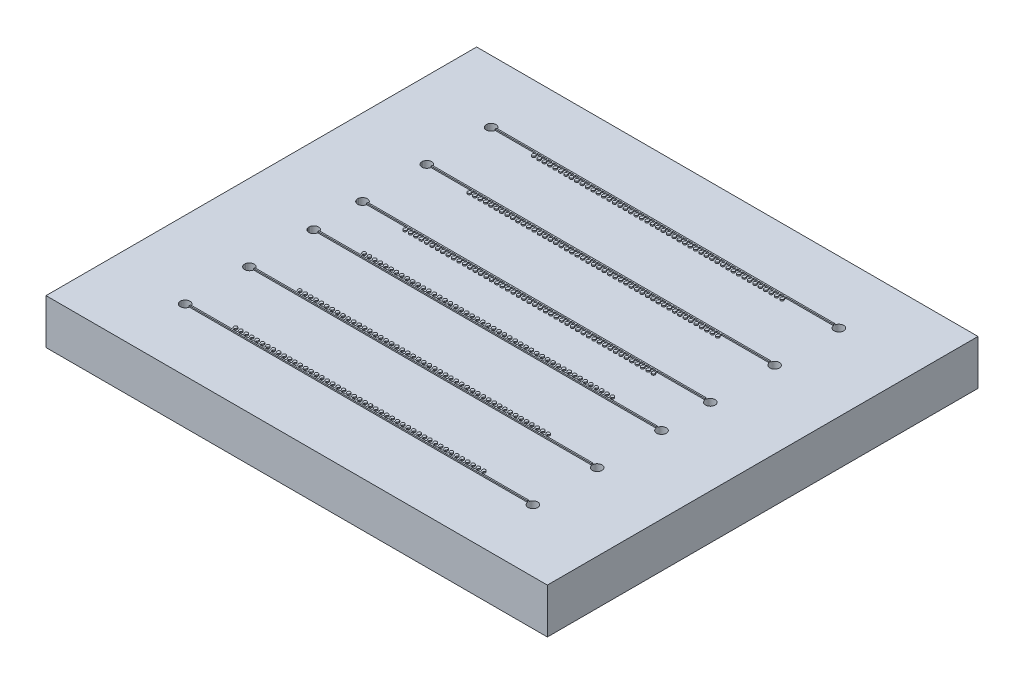
SolidWorks part; units mm, degrees
ref_plane "Front Plane" through (0, 0, 0) normal (0, 0, 1) x (1, 0, 0)
ref_plane "Top Plane" through (0, 0, 0) normal (0, 1, 0) x (1, 0, 0)
ref_plane "Right Plane" through (0, 0, 0) normal (1, 0, 0) x (0, 0, -1)
sketch "Sketch1" plane through (0, 0, 0) normal (0, 1, 0) x (1, 0, 0)
  line L1 (-19.5, 16.75) -> (19.5, 16.75)
  line L2 (-19.5, 16.75) -> (-19.5, -16.75)
  line L3 (-19.5, -16.75) -> (19.5, -16.75)
  line L4 (19.5, 16.75) -> (19.5, -16.75)
  line L5 (-19.5, 16.75) -> (19.5, -16.75) construction
  line L6 (-19.5, -16.75) -> (19.5, 16.75) construction
  point P0 (0, 0)
  dimension "D1" = 33.5
  dimension "D2" = 39
extrude "Boss-Extrude1" add sketch "Sketch1" along normal blind 3.5
sketch "Sketch2" plane through (0, 3.5, 0) normal (0, 1, 0) x (1, 0, 0)
  line L0 (0, -1000) -> (0, 49000) construction
  line L1 (-13.1533, 12.4873) -> (-13.1533, 11.3127) construction
  line L2 (-9.02, 11.85) -> (-9.02, 11.71)
  line L3 (-19.5, 0) -> (19.5, 0) construction
  line L4 (-19.5, 16.75) -> (-19.5, -16.75) construction
  line L5 (19.5, -16.75) -> (19.5, 16.75) construction
  line L6 (-9.12, 11.85) -> (-9.12, 11.71)
  line L7 (-9.44, 11.85) -> (-9.12, 11.85)
  line L8 (-13.9, 11.95) -> (13.9, 11.95)
  line L9 (19.5, 16.75) -> (-19.5, 16.75) construction
  line L10 (-13.9, 11.95) -> (-13.9, 11.85)
  line L11 (-13.9, 11.85) -> (-9.96, 11.85)
  line L12 (-9.96, 11.85) -> (-9.96, 11.71)
  line L13 (-9.86, 11.71) -> (-9.86, 11.85)
  line L14 (-9.86, 11.85) -> (-9.54, 11.85)
  line L15 (-9.54, 11.85) -> (-9.54, 11.71)
  line L16 (-9.44, 11.85) -> (-9.44, 11.71)
  line L17 (-8.6, 11.85) -> (-8.6, 11.71)
  line L18 (-8.7, 11.85) -> (-8.7, 11.71)
  line L19 (-9.02, 11.85) -> (-8.7, 11.85)
  line L20 (-8.18, 11.85) -> (-8.18, 11.71)
  line L21 (-8.28, 11.85) -> (-8.28, 11.71)
  line L22 (-8.6, 11.85) -> (-8.28, 11.85)
  line L23 (-7.76, 11.85) -> (-7.76, 11.71)
  line L24 (-7.86, 11.85) -> (-7.86, 11.71)
  line L25 (-8.18, 11.85) -> (-7.86, 11.85)
  line L26 (-7.34, 11.85) -> (-7.34, 11.71)
  line L27 (-7.44, 11.85) -> (-7.44, 11.71)
  line L28 (-7.76, 11.85) -> (-7.44, 11.85)
  line L29 (-6.92, 11.85) -> (-6.92, 11.71)
  line L30 (-7.02, 11.85) -> (-7.02, 11.71)
  line L31 (-7.34, 11.85) -> (-7.02, 11.85)
  line L32 (-6.5, 11.85) -> (-6.5, 11.71)
  line L33 (-6.6, 11.85) -> (-6.6, 11.71)
  line L34 (-6.92, 11.85) -> (-6.6, 11.85)
  line L35 (-6.08, 11.85) -> (-6.08, 11.71)
  line L36 (-6.18, 11.85) -> (-6.18, 11.71)
  line L37 (-6.5, 11.85) -> (-6.18, 11.85)
  line L38 (-5.66, 11.85) -> (-5.66, 11.71)
  line L39 (-5.76, 11.85) -> (-5.76, 11.71)
  line L40 (-6.08, 11.85) -> (-5.76, 11.85)
  line L41 (-5.24, 11.85) -> (-5.24, 11.71)
  line L42 (-5.34, 11.85) -> (-5.34, 11.71)
  line L43 (-5.66, 11.85) -> (-5.34, 11.85)
  line L44 (-4.82, 11.85) -> (-4.82, 11.71)
  line L45 (-4.92, 11.85) -> (-4.92, 11.71)
  line L46 (-5.24, 11.85) -> (-4.92, 11.85)
  line L47 (-4.4, 11.85) -> (-4.4, 11.71)
  line L48 (-4.5, 11.85) -> (-4.5, 11.71)
  line L49 (-4.82, 11.85) -> (-4.5, 11.85)
  line L50 (-3.98, 11.85) -> (-3.98, 11.71)
  line L51 (-4.08, 11.85) -> (-4.08, 11.71)
  line L52 (-4.4, 11.85) -> (-4.08, 11.85)
  line L53 (-3.56, 11.85) -> (-3.56, 11.71)
  line L54 (-3.66, 11.85) -> (-3.66, 11.71)
  line L55 (-3.98, 11.85) -> (-3.66, 11.85)
  line L56 (-3.14, 11.85) -> (-3.14, 11.71)
  line L57 (-3.24, 11.85) -> (-3.24, 11.71)
  line L58 (-3.56, 11.85) -> (-3.24, 11.85)
  line L59 (-2.72, 11.85) -> (-2.72, 11.71)
  line L60 (-2.82, 11.85) -> (-2.82, 11.71)
  line L61 (-3.14, 11.85) -> (-2.82, 11.85)
  line L62 (-2.3, 11.85) -> (-2.3, 11.71)
  line L63 (-2.4, 11.85) -> (-2.4, 11.71)
  line L64 (-2.72, 11.85) -> (-2.4, 11.85)
  line L65 (-1.88, 11.85) -> (-1.88, 11.71)
  line L66 (-1.98, 11.85) -> (-1.98, 11.71)
  line L67 (-2.3, 11.85) -> (-1.98, 11.85)
  line L68 (-1.46, 11.85) -> (-1.46, 11.71)
  line L69 (-1.56, 11.85) -> (-1.56, 11.71)
  line L70 (-1.88, 11.85) -> (-1.56, 11.85)
  line L71 (-1.04, 11.85) -> (-1.04, 11.71)
  line L72 (-1.14, 11.85) -> (-1.14, 11.71)
  line L73 (-1.46, 11.85) -> (-1.14, 11.85)
  line L74 (-0.62, 11.85) -> (-0.62, 11.71)
  line L75 (-0.72, 11.85) -> (-0.72, 11.71)
  line L76 (-1.04, 11.85) -> (-0.72, 11.85)
  line L77 (-0.2, 11.85) -> (-0.2, 11.71)
  line L78 (-0.3, 11.85) -> (-0.3, 11.71)
  line L79 (-0.62, 11.85) -> (-0.3, 11.85)
  line L80 (0.22, 11.85) -> (0.22, 11.71)
  line L81 (0.12, 11.85) -> (0.12, 11.71)
  line L82 (-0.2, 11.85) -> (0.12, 11.85)
  line L83 (0.64, 11.85) -> (0.64, 11.71)
  line L84 (0.54, 11.85) -> (0.54, 11.71)
  line L85 (0.22, 11.85) -> (0.54, 11.85)
  line L86 (1.06, 11.85) -> (1.06, 11.71)
  line L87 (0.96, 11.85) -> (0.96, 11.71)
  line L88 (0.64, 11.85) -> (0.96, 11.85)
  line L89 (1.48, 11.85) -> (1.48, 11.71)
  line L90 (1.38, 11.85) -> (1.38, 11.71)
  line L91 (1.06, 11.85) -> (1.38, 11.85)
  line L92 (1.9, 11.85) -> (1.9, 11.71)
  line L93 (1.8, 11.85) -> (1.8, 11.71)
  line L94 (1.48, 11.85) -> (1.8, 11.85)
  line L95 (2.32, 11.85) -> (2.32, 11.71)
  line L96 (2.22, 11.85) -> (2.22, 11.71)
  line L97 (1.9, 11.85) -> (2.22, 11.85)
  line L98 (2.74, 11.85) -> (2.74, 11.71)
  line L99 (2.64, 11.85) -> (2.64, 11.71)
  line L100 (2.32, 11.85) -> (2.64, 11.85)
  line L101 (3.16, 11.85) -> (3.16, 11.71)
  line L102 (3.06, 11.85) -> (3.06, 11.71)
  line L103 (2.74, 11.85) -> (3.06, 11.85)
  line L104 (3.58, 11.85) -> (3.58, 11.71)
  line L105 (3.48, 11.85) -> (3.48, 11.71)
  line L106 (3.16, 11.85) -> (3.48, 11.85)
  line L107 (4, 11.85) -> (4, 11.71)
  line L108 (3.9, 11.85) -> (3.9, 11.71)
  line L109 (3.58, 11.85) -> (3.9, 11.85)
  line L110 (4.42, 11.85) -> (4.42, 11.71)
  line L111 (4.32, 11.85) -> (4.32, 11.71)
  line L112 (4, 11.85) -> (4.32, 11.85)
  line L113 (4.84, 11.85) -> (4.84, 11.71)
  line L114 (4.74, 11.85) -> (4.74, 11.71)
  line L115 (4.42, 11.85) -> (4.74, 11.85)
  line L116 (5.26, 11.85) -> (5.26, 11.71)
  line L117 (5.16, 11.85) -> (5.16, 11.71)
  line L118 (4.84, 11.85) -> (5.16, 11.85)
  line L119 (5.68, 11.85) -> (5.68, 11.71)
  line L120 (5.58, 11.85) -> (5.58, 11.71)
  line L121 (5.26, 11.85) -> (5.58, 11.85)
  line L122 (6.1, 11.85) -> (6.1, 11.71)
  line L123 (6, 11.85) -> (6, 11.71)
  line L124 (5.68, 11.85) -> (6, 11.85)
  line L125 (6.52, 11.85) -> (6.52, 11.71)
  line L126 (6.42, 11.85) -> (6.42, 11.71)
  line L127 (6.1, 11.85) -> (6.42, 11.85)
  line L128 (6.94, 11.85) -> (6.94, 11.71)
  line L129 (6.84, 11.85) -> (6.84, 11.71)
  line L130 (6.52, 11.85) -> (6.84, 11.85)
  line L131 (7.36, 11.85) -> (7.36, 11.71)
  line L132 (7.26, 11.85) -> (7.26, 11.71)
  line L133 (6.94, 11.85) -> (7.26, 11.85)
  line L134 (7.78, 11.85) -> (7.78, 11.71)
  line L135 (7.68, 11.85) -> (7.68, 11.71)
  line L136 (7.36, 11.85) -> (7.68, 11.85)
  line L137 (8.2, 11.85) -> (8.2, 11.71)
  line L138 (8.1, 11.85) -> (8.1, 11.71)
  line L139 (7.78, 11.85) -> (8.1, 11.85)
  line L140 (8.62, 11.85) -> (8.62, 11.71)
  line L141 (8.52, 11.85) -> (8.52, 11.71)
  line L142 (8.2, 11.85) -> (8.52, 11.85)
  line L143 (9.04, 11.85) -> (9.04, 11.71)
  line L144 (8.94, 11.85) -> (8.94, 11.71)
  line L145 (8.62, 11.85) -> (8.94, 11.85)
  line L146 (9.46, 11.85) -> (9.46, 11.71)
  line L147 (9.36, 11.85) -> (9.36, 11.71)
  line L148 (9.04, 11.85) -> (9.36, 11.85)
  line L149 (-9.44, 11.85) -> (-9.02, 11.85) construction
  line L150 (9.46, 11.85) -> (13.9, 11.85)
  line L151 (13.9, 11.85) -> (13.9, 11.95)
  line L152 (13.1533, 12.6013) -> (13.1533, 11.1987) construction
  arc A0 (-9.96, 11.71) -> (-9.86, 11.71) centre (-9.91, 11.5965) ccw
  arc A1 (-9.54, 11.71) -> (-9.44, 11.71) centre (-9.49, 11.5965) ccw
  circle A2 centre (-13.5283, 11.9) radius 0.375
  arc A3 (-9.12, 11.71) -> (-9.02, 11.71) centre (-9.07, 11.5965) ccw
  arc A4 (-8.7, 11.71) -> (-8.6, 11.71) centre (-8.65, 11.5965) ccw
  arc A5 (-8.28, 11.71) -> (-8.18, 11.71) centre (-8.23, 11.5965) ccw
  arc A6 (-7.86, 11.71) -> (-7.76, 11.71) centre (-7.81, 11.5965) ccw
  arc A7 (-7.44, 11.71) -> (-7.34, 11.71) centre (-7.39, 11.5965) ccw
  arc A8 (-7.02, 11.71) -> (-6.92, 11.71) centre (-6.97, 11.5965) ccw
  arc A9 (-6.6, 11.71) -> (-6.5, 11.71) centre (-6.55, 11.5965) ccw
  arc A10 (-6.18, 11.71) -> (-6.08, 11.71) centre (-6.13, 11.5965) ccw
  arc A11 (-5.76, 11.71) -> (-5.66, 11.71) centre (-5.71, 11.5965) ccw
  arc A12 (-5.34, 11.71) -> (-5.24, 11.71) centre (-5.29, 11.5965) ccw
  arc A13 (-4.92, 11.71) -> (-4.82, 11.71) centre (-4.87, 11.5965) ccw
  arc A14 (-4.5, 11.71) -> (-4.4, 11.71) centre (-4.45, 11.5965) ccw
  arc A15 (-4.08, 11.71) -> (-3.98, 11.71) centre (-4.03, 11.5965) ccw
  arc A16 (-3.66, 11.71) -> (-3.56, 11.71) centre (-3.61, 11.5965) ccw
  arc A17 (-3.24, 11.71) -> (-3.14, 11.71) centre (-3.19, 11.5965) ccw
  arc A18 (-2.82, 11.71) -> (-2.72, 11.71) centre (-2.77, 11.5965) ccw
  arc A19 (-2.4, 11.71) -> (-2.3, 11.71) centre (-2.35, 11.5965) ccw
  arc A20 (-1.98, 11.71) -> (-1.88, 11.71) centre (-1.93, 11.5965) ccw
  arc A21 (-1.56, 11.71) -> (-1.46, 11.71) centre (-1.51, 11.5965) ccw
  arc A22 (-1.14, 11.71) -> (-1.04, 11.71) centre (-1.09, 11.5965) ccw
  arc A23 (-0.72, 11.71) -> (-0.62, 11.71) centre (-0.67, 11.5965) ccw
  arc A24 (-0.3, 11.71) -> (-0.2, 11.71) centre (-0.25, 11.5965) ccw
  arc A25 (0.12, 11.71) -> (0.22, 11.71) centre (0.17, 11.5965) ccw
  arc A26 (0.54, 11.71) -> (0.64, 11.71) centre (0.59, 11.5965) ccw
  arc A27 (0.96, 11.71) -> (1.06, 11.71) centre (1.01, 11.5965) ccw
  arc A28 (1.38, 11.71) -> (1.48, 11.71) centre (1.43, 11.5965) ccw
  arc A29 (1.8, 11.71) -> (1.9, 11.71) centre (1.85, 11.5965) ccw
  arc A30 (2.22, 11.71) -> (2.32, 11.71) centre (2.27, 11.5965) ccw
  arc A31 (2.64, 11.71) -> (2.74, 11.71) centre (2.69, 11.5965) ccw
  arc A32 (3.06, 11.71) -> (3.16, 11.71) centre (3.11, 11.5965) ccw
  arc A33 (3.48, 11.71) -> (3.58, 11.71) centre (3.53, 11.5965) ccw
  arc A34 (3.9, 11.71) -> (4, 11.71) centre (3.95, 11.5965) ccw
  arc A35 (4.32, 11.71) -> (4.42, 11.71) centre (4.37, 11.5965) ccw
  arc A36 (4.74, 11.71) -> (4.84, 11.71) centre (4.79, 11.5965) ccw
  arc A37 (5.16, 11.71) -> (5.26, 11.71) centre (5.21, 11.5965) ccw
  arc A38 (5.58, 11.71) -> (5.68, 11.71) centre (5.63, 11.5965) ccw
  arc A39 (6, 11.71) -> (6.1, 11.71) centre (6.05, 11.5965) ccw
  arc A40 (6.42, 11.71) -> (6.52, 11.71) centre (6.47, 11.5965) ccw
  arc A41 (6.84, 11.71) -> (6.94, 11.71) centre (6.89, 11.5965) ccw
  arc A42 (7.26, 11.71) -> (7.36, 11.71) centre (7.31, 11.5965) ccw
  arc A43 (7.68, 11.71) -> (7.78, 11.71) centre (7.73, 11.5965) ccw
  arc A44 (8.1, 11.71) -> (8.2, 11.71) centre (8.15, 11.5965) ccw
  arc A45 (8.52, 11.71) -> (8.62, 11.71) centre (8.57, 11.5965) ccw
  arc A46 (8.94, 11.71) -> (9.04, 11.71) centre (8.99, 11.5965) ccw
  arc A47 (9.36, 11.71) -> (9.46, 11.71) centre (9.41, 11.5965) ccw
  circle A48 centre (13.5283, 11.9) radius 0.375
  point P11 (0, 11.95)
  point P19 (-13.9, 11.9)
  point P33 (-13.1533, 11.9)
  point P309 (13.1533, 11.9)
  dimension "D4" = 0.1
  dimension "D13" = 0.248
  dimension "D14" = 0.75
  dimension "D17" = 0.75
  dimension "D1" = 4.8
  dimension "D2" = 27.8
  dimension "D3" = 0.1
  dimension "D5" = 3.94
  dimension "D6" = 0.14
  dimension "D7" = 0.14
  dimension "D9" = 0.32
  dimension "D10" = 0.14
  dimension "D11" = 0.14
  dimension "D12" = 0.1
  dimension "D16" = 0.42
  dimension "D15" = 46
extrude "Boss-Extrude3" add sketch "Sketch2" along normal blind 0.1 contours A48 L8 A2 L11 L12 A0 L13 L14 L15 A1 L16 L7 L6 A3 L2 L19 L18 A4 L17 L22 L21 A5 L20 L25 L24 A6 L23 L28 L27 A7 L26 L31 L30 A8 L29 L34 L33 A9 L32 L37 L36 A10 L35 L40 L39 A11 L38 L43 L42 A12 L41 region at (-9.0463, 3.5, -11.78)
extrude "Cut-Extrude1" cut sketch "Sketch2<9>" against normal up to next contours L8 A2 | L11 A2 L8 L10 | L11 A2 | L8 A48 | L8 A48 L150 L151 | L150 A48 region at (-13.5283, 3.5, -11.7135) region at (-13.5272, 3.5, -11.9) region at (-13.5283, 3.5, -12.0865) region at (13.5283, 3.5, -12.0865) region at (13.5272, 3.5, -11.9) region at (13.5283, 3.5, -11.7135)
sketch "Sketch2<9>" plane through (0, 3.5, 0) normal (0, 1, 0) x (1, 0, 0) same geometry as "Sketch2"
pattern_linear "LPattern3" count 3 spacing 5 along (0, 0, 1) of "Cut-Extrude1", "Boss-Extrude3"
sketch "Sketch3" plane through (0, 3.5, 0) normal (0, 1, 0) x (1, 0, 0)
  line L0 (-19.5, 0) -> (19.5, 0) construction
  line L1 (-19.5, 16.75) -> (-19.5, -16.75) construction
  line L2 (19.5, -16.75) -> (19.5, 16.75) construction
mirror "Mirror1" about plane through (0, 0, 0) normal (0, 0, 1) of "LPattern3"
